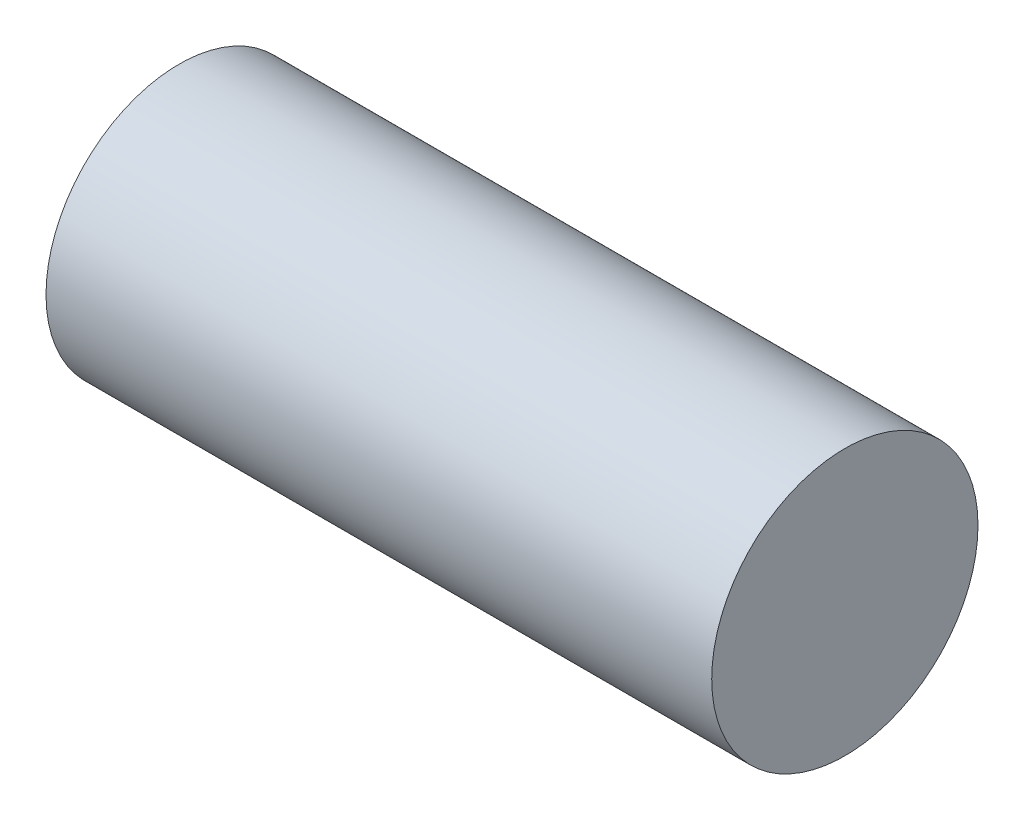
SolidWorks part; units mm, degrees
ref_plane "Front Plane" through (0, 0, 0) normal (0, 0, 1) x (1, 0, 0)
ref_plane "Top Plane" through (0, 0, 0) normal (0, 1, 0) x (1, 0, 0)
ref_plane "Right Plane" through (0, 0, 0) normal (1, 0, 0) x (0, 0, -1)
sketch "Sketch1" plane through (0, 0, 0) normal (0, 1, 0) x (1, 0, 0)
  line L0 (-6, 0) -> (6, 0) construction
  line L1 (6, -20) -> (-6, -20)
  line L2 (6, -20) -> (6, 20)
  line L3 (6, 20) -> (-6, 20)
  line L4 (-6, -20) -> (-6, 20)
  line L5 (6, -20) -> (-6, 20) construction
  line L6 (6, 20) -> (-6, -20) construction
  line L7 (0, -5) -> (0, 5) construction
  circle A0 centre (0, 5) radius 1
  circle A1 centre (0, -5) radius 1
  point P0 (0, 0)
  dimension "D3" = 5
  dimension "D4" = 2
  dimension "D1" = 40
  dimension "D2" = 12
extrude "Hinge " [suppressed] add sketch "Sketch1" along normal blind 5
sketch "Sketch2" [suppressed] plane through (6, 0, 0) normal (1, 0, 0) x (0, 0, -1)
  line L0 (0, 0) -> (0, 5) construction
  line L1 (-20, 0) -> (20, 0) construction
  line L2 (-20, 5) -> (20, 5) construction
  line L3 (-20, 2.5) -> (20, 2.5) construction
  line L4 (-20, 5) -> (-20, 0) construction
  line L5 (20, 5) -> (20, 0) construction
  line L7 (-6, 0) -> (-16, 0)
  line L8 (-6, 0) -> (-6, 5)
  line L9 (-6, 5) -> (-16, 5)
  line L10 (-16, 0) -> (-16, 5)
  line L11 (-6, 0) -> (-16, 5) construction
  line L12 (-6, 5) -> (-16, 0) construction
  line L13 (16, 0) -> (6, 0)
  line L14 (16, 0) -> (16, 5)
  line L15 (16, 5) -> (6, 5)
  line L16 (6, 0) -> (6, 5)
  line L17 (16, 0) -> (6, 5) construction
  line L18 (16, 5) -> (6, 0) construction
  point P12 (-11, 2.5)
  point P17 (11, 2.5)
  dimension "D1" = 6
  dimension "D2" = 5
  dimension "D3" = 10
extrude "Hinge Extrude 1" [suppressed] add sketch "Sketch2" along normal blind 5
sketch "Sketch3" [suppressed] plane through (0, 0, -16) normal (0, 0, -1) x (-1, 0, 0)
  line L0 (-8.5, 0) -> (-8.5, 5) construction
  line L1 (-11, 0) -> (-6, 0) construction
  line L2 (-11, 5) -> (-6, 5) construction
  circle A0 centre (-8.5, 2.5) radius 1
  dimension "D1" = 2
extrude "Hole Cut 1" [suppressed] cut sketch "Sketch3" against normal through all both and the other way through all
fillet "Fillet Holes 1" [suppressed] radius 0.5
chamfer "Chamfer 1" [suppressed] distance 1.5 angle 45
sketch "Sketch4" [suppressed] plane through (6, 0, 0) normal (1, 0, 0) x (0, 0, -1)
  line L0 (0, 0) -> (0, 5) construction
  line L1 (-20, 0) -> (20, 0) construction
  line L2 (-20, 5) -> (20, 5) construction
  line L4 (5, 0) -> (-5, 0)
  line L5 (5, 0) -> (5, 5)
  line L6 (5, 5) -> (-5, 5)
  line L7 (-5, 0) -> (-5, 5)
  line L8 (5, 0) -> (-5, 5) construction
  line L9 (5, 5) -> (-5, 0) construction
  point P6 (0, 2.5)
  dimension "D1" = 5
  dimension "D2" = 10
extrude "Hinge Extrude 2" [suppressed] add sketch "Sketch4" along normal blind 5
sketch "Sketch6" [suppressed] plane through (0, 0, -5) normal (0, 0, -1) x (-1, 0, 0)
  line L0 (-8.5, 0) -> (-8.5, 5) construction
  line L1 (-11, 0) -> (-6, 0) construction
  line L2 (-11, 5) -> (-6, 5) construction
  circle A0 centre (-8.5, 2.5) radius 1
  dimension "D1" = 2
extrude "Hole Cut 2 " [suppressed] cut sketch "Sketch6" against normal through all
chamfer "Chamfer2" [suppressed] distance 1.5 angle 45
fillet "Fillet Holes 2" [suppressed] radius 0.5
sketch "Sketch7" [suppressed] plane through (0, 0, 0) normal (0, 0, 1) x (1, 0, 0)
  circle A0 centre (0, 0) radius 1
  dimension "D1" = 2
extrude "Hinge Holder" [suppressed] add sketch "Sketch7" along normal blind 40
sketch "Sketch8" [suppressed] plane through (0, 0, 0) normal (0, 0, -1) x (-1, 0, 0)
  circle A0 centre (0, 0) radius 1.5
  dimension "D1" = 3
extrude "Hinge Holder Cap" [suppressed] add sketch "Sketch8" along normal blind 1
chamfer "Hinge Holder Cap Fillet" [suppressed] distance 0.5 angle 45
sketch "Sketch9" plane through (0, 0, 0) normal (1, 0, 0) x (0, 0, -1)
  circle A0 centre (0, 0) radius 2
  dimension "D1" = 4
extrude "Boss-Extrude1" add sketch "Sketch9" along normal blind 10
